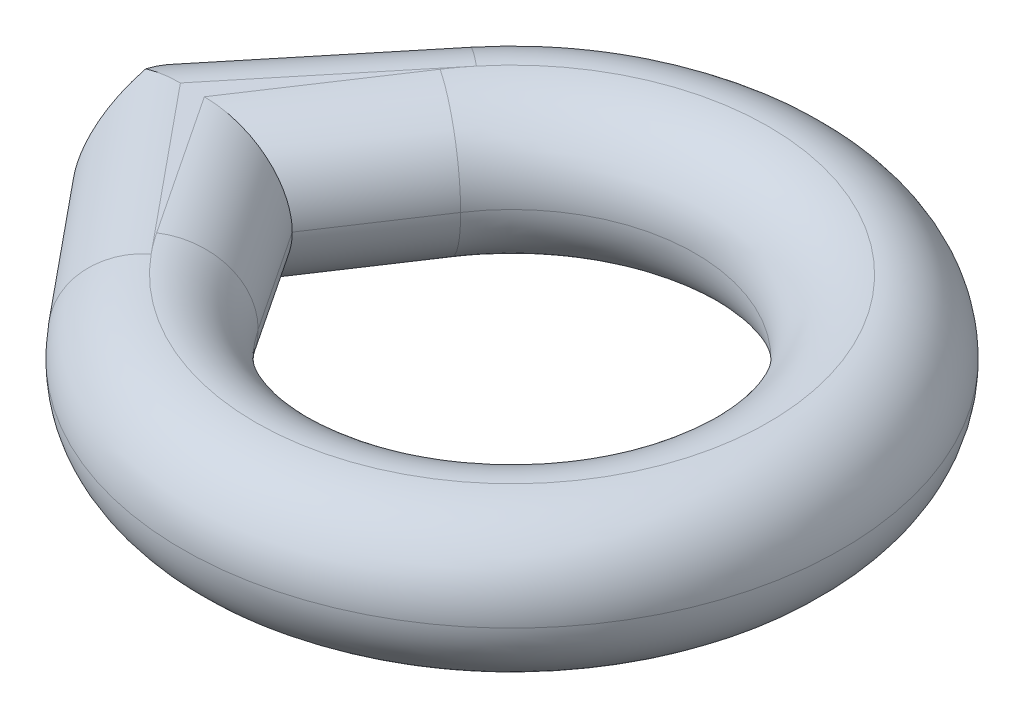
SolidWorks part; units mm, degrees
ref_plane "Front Plane" through (0, 0, 0) normal (0, 0, 1) x (1, 0, 0)
ref_plane "Top Plane" through (0, 0, 0) normal (0, 1, 0) x (1, 0, 0)
ref_plane "Right Plane" through (0, 0, 0) normal (1, 0, 0) x (0, 0, -1)
sketch "Sketch1" plane through (0, 0, 0) normal (0, 1, 0) x (1, 0, 0)
  line L0 (0, 0) -> (-5, 0) construction
  line L1 (-5, 0) -> (-5, 1)
  line L2 (-5, 0) -> (-5, -1)
  line L3 (-5, 1) -> (-3.4792, 2.854)
  line L4 (-5, -1) -> (-3.4792, -2.854)
  line L5 (-3, 0) -> (-2.0833, 1.3819)
  line L6 (-3, 0) -> (-2.0833, -1.3819)
  arc A0 (-2.0833, -1.3819) -> (-2.0833, 1.3819) centre (0, 0) ccw
  circle A1 centre (0, 0) radius 4.5 construction
  arc A2 (-3.4792, 2.854) -> (-3.4792, -2.854) centre (0, 0) cw
  point P13 (0, 0)
  dimension "D2" = 9
  dimension "D1" = 5
  dimension "D3" = 2
  dimension "D4" = 5
  dimension "D5" = 2
extrude "Boss-Extrude1" add sketch "Sketch1" along normal blind 1 and the other way blind 1 contours A2 L3 L1 L2 L4 A0 L6 L5 region at (-4.8691, 0, -0.5)
ref_point "SpringWireCentre"
fillet "Fillet1" radius 1 12 edges at (-4.2396, 1, -1.927) (2.5, 1, 0) (4.5, 1, 0) (4.5, -1, 0) (-4.2396, -1, -1.927) (-4.2396, -1, 1.927) (-4.2396, 1, 1.927) (-2.5417, -1, 0.691) (2.5, -1, 0) (-2.5417, -1, -0.691) (-2.5417, 1, 0.691) (-2.5417, 1, -0.691)
ref_point "CableCentre"
equation "\"SpringWireDiameter\"= 5"
equation "\"D1@Sketch1\"=\"SpringWireDiameter\""
equation "\"CableDiameter\"=2"
equation "\"D2@Sketch1\"=\"SpringWireDiameter\"+\"CableDiameter\"*2"
equation "\"D3@Sketch1\"=\"CableDiameter\""
equation "\"D5@Sketch1\"=\"CableDiameter\""
equation "\"D1@Boss-Extrude1\"=\"CableDiameter\"/2"
equation "\"D2@Boss-Extrude1\"=\"CableDiameter\"/2"
equation "\"D1@Fillet1\"=\"CableDiameter\"/2"
equation "\"D4@Sketch1\"=\"SpringWireDiameter\""
